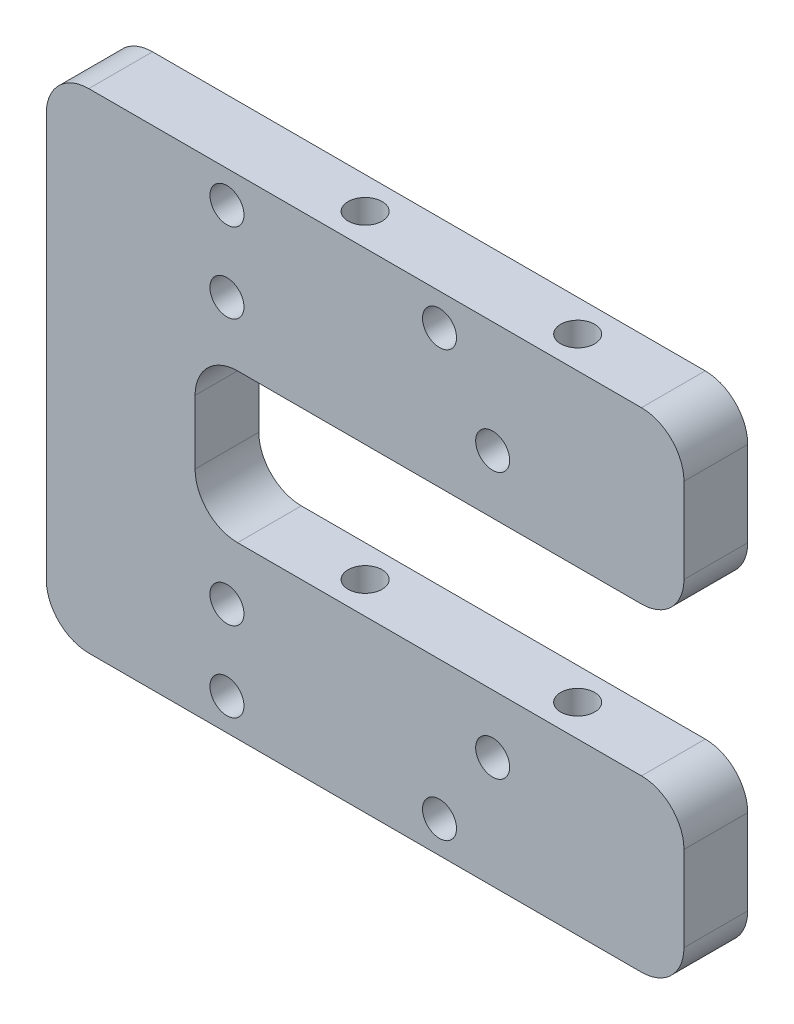
SolidWorks part; units mm, degrees
material "3003 合金"
ref_plane "前视基准面" through (0, 0, 0) normal (0, 0, 1) x (1, 0, 0)
ref_plane "上视基准面" through (0, 0, 0) normal (0, 1, 0) x (1, 0, 0)
ref_plane "右视基准面" through (0, 0, 0) normal (1, 0, 0) x (0, 0, -1)
other "Configuration Table"
sketch "草图1" plane through (0, 0, 0) normal (0, 0, 1) x (1, 0, 0)
  line L0 (0, 23) -> (95.8228, 23) construction
  line L1 (0, 0) -> (60, 0)
  line L2 (0, 0) -> (0, 46)
  line L3 (0, 46) -> (60, 46)
  line L4 (60, 0) -> (60, 16)
  line L5 (14, 16) -> (60, 16)
  line L7 (14, 16) -> (14, 30)
  line L8 (14, 30) -> (60, 30)
  line L10 (60, 30) -> (60, 46)
  line L11 (14, 16) -> (60, 16)
  circle A0 centre (17, 35.5) radius 1.6
  circle A1 centre (42, 35.5) radius 1.6
  circle A2 centre (42, 10.5) radius 1.6
  circle A3 centre (17, 10.5) radius 1.6
  dimension "D6" = 25
  dimension "3.2" = 3.2
  dimension "D7" = 25
  dimension "D8" = 17
  dimension "D1" = 60
  dimension "D2" = 46
  dimension "D3" = 46
  dimension "D4" = 7
  dimension "D5" = 2
extrude "凸台-拉伸1" add sketch "草图1" along normal blind 6 contours L2 L0 L7 L8 L10 L3 A0 A1 | L0 L2 L1 L4 L5 L7 A2 A3 region at (27.8444, 36.9569, 0) region at (27.8444, 9.0431, 0)
fillet "圆角1" radius 4 8 edges at (0, 46, 3) (60, 46, 3) (60, 30, 3) (14, 30, 3) (14, 16, 3) (60, 16, 3) (0, 0, 3) (60, 0, 3)
sketch "草图2" plane through (0, 0, 6) normal (0, 0, 1) x (1, 0, 0)
  line L0 (0, 4) -> (0, 42) construction
  line L1 (0, 23) -> (82.9703, 23) construction
  circle A0 centre (17, 3) radius 1.6
  circle A2 centre (37, 3) radius 1.6
  circle A3 centre (37, 43) radius 1.6
  circle A4 centre (17, 43) radius 1.6
  dimension "D1" = 3.2
  dimension "D2" = 17
  dimension "D4" = 40
  dimension "D5" = 20
  dimension "D3" = 2
extrude "切除-拉伸1" cut sketch "草图2" against normal blind 10
sketch "草图3" plane through (0, 46, 0) normal (0, 1, 0) x (1, 0, 0)
  line L0 (0, -6) -> (0, 0) construction
  line L1 (4, 0) -> (56, 0) construction
  circle A0 centre (27, -3) radius 1.6
  circle A1 centre (47, -3) radius 1.6
  point P8 (30, 0)
  dimension "D1" = 3.2
  dimension "D4" = 20
  dimension "D5" = 3
  dimension "D2" = 27
  dimension "D3" = 2
extrude "切除-拉伸2" cut sketch "草图3" against normal blind 67
